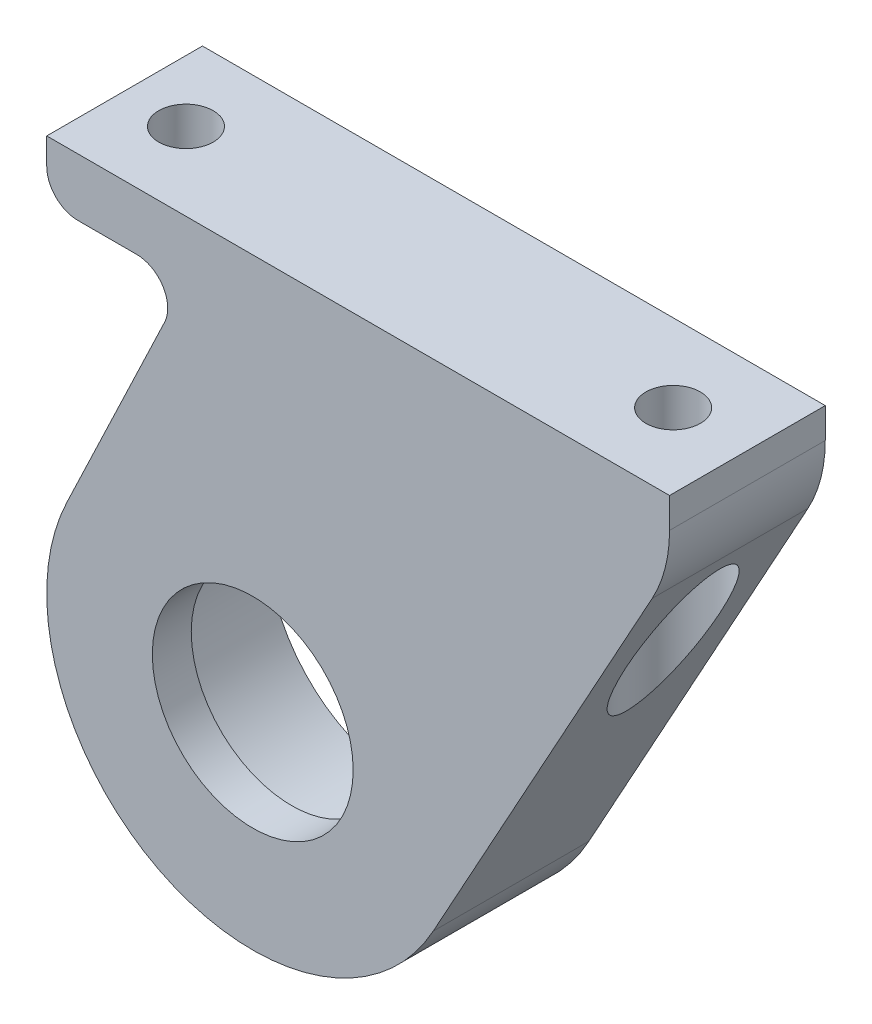
SolidWorks part; units mm, degrees
ref_plane "Front Plane" through (0, 0, 0) normal (0, 0, 1) x (1, 0, 0)
ref_plane "Top Plane" through (0, 0, 0) normal (0, 1, 0) x (1, 0, 0)
ref_plane "Right Plane" through (0, 0, 0) normal (1, 0, 0) x (0, 0, -1)
sketch "Sketch1" plane through (0, 0, 0) normal (0, 0, 1) x (1, 0, 0)
  line L0 (-34.1926, 20.0279) -> (32.8074, 20.0279) construction
  line L1 (12.8074, 20.0279) -> (12.8074, -17.6407) construction
  line L2 (-18.482, 20.0279) -> (-18.482, 5.8436) construction
  line L3 (-22.4232, 18.3246) -> (-22.4232, 20.0279)
  line L4 (2.3971, -11.7942) -> (16.4605, 13.7444)
  line L5 (17.5768, 18.0858) -> (17.5768, 20.0279)
  line L6 (17.5768, 20.0279) -> (-22.4232, 20.0279)
  line L7 (-21.1339, 0.2848) -> (-14.8468, 13.4634)
  line L8 (-20.4232, 16.3246) -> (-16.6519, 16.3246)
  circle A0 centre (-9.1926, -5.4121) radius 9.05
  arc A1 (-21.1339, 0.2848) -> (2.3971, -11.7942) centre (-9.1926, -5.4121) ccw
  arc A2 (16.4605, 13.7444) -> (17.5768, 18.0858) centre (8.5768, 18.0858) ccw
  arc A3 (-22.4232, 18.3246) -> (-20.4232, 16.3246) centre (-20.4232, 18.3246) ccw
  arc A4 (-16.6519, 16.3246) -> (-14.8468, 13.4634) centre (-16.6519, 14.3246) cw
  point P19 (0, 0)
  point P22 (0, 0)
  dimension "D1" = 9
  dimension "D2" = 2
  dimension "D3" = 40
  dimension "D4" = 3.9413
  dimension "D5" = 31.2894
extrude "Boss-Extrude1" add sketch "Sketch1" along normal blind 10
sketch "Sketch2" plane through (0, 0, 10) normal (0, 0, 1) x (1, 0, 0)
  circle A0 centre (-9.1926, -5.4121) radius 6.45
  circle A1 centre (-9.1926, -5.4121) radius 10.9432
  dimension "D1" = 12.9
extrude "Boss-Extrude2" add sketch "Sketch2" against normal blind 2.5
sketch "Sketch3" plane through (0, 20.0279, 0) normal (0, 1, 0) x (1, 0, 0)
  line L0 (-18.482, -13.5292) -> (-18.482, 5.9874) construction
  line L1 (12.8068, 5.317) -> (12.8068, -13.5292) construction
  line L2 (-22.4232, -10) -> (-22.4232, 0) construction
  line L3 (17.5768, -10) -> (17.5768, 0) construction
  line L4 (-18.482, -5) -> (12.8068, -5) construction
  line L5 (17.5768, -10) -> (-22.4232, -10) construction
  circle A0 centre (-18.482, -5) radius 1.75
  circle A1 centre (12.8068, -5) radius 1.75
  dimension "D4" = 3.5
  dimension "D1" = 3.9413
  dimension "D2" = 4.77
  dimension "D3" = 5
sketch "Sketch5" plane through (0, 16.3246, 0) normal (0, -1, 0) x (1, 0, 0)
  circle A0 centre (-18.482, 5) radius 3
extrude "Cut-Extrude3" cut sketch "Sketch5" along normal blind 11.7 from offset 0.7 offset against normal yes
extrude "Cut-Extrude4" cut sketch "Sketch3" against normal blind 14
sketch "Sketch7" plane through (0, 20.0279, 0) normal (0, 1, 0) x (1, 0, 0)
  circle A0 centre (12.8068, -5) radius 3
  dimension "D1" = 6
extrude "Cut-Extrude5" cut sketch "Sketch7" against normal through all from offset 3 offset against normal yes
